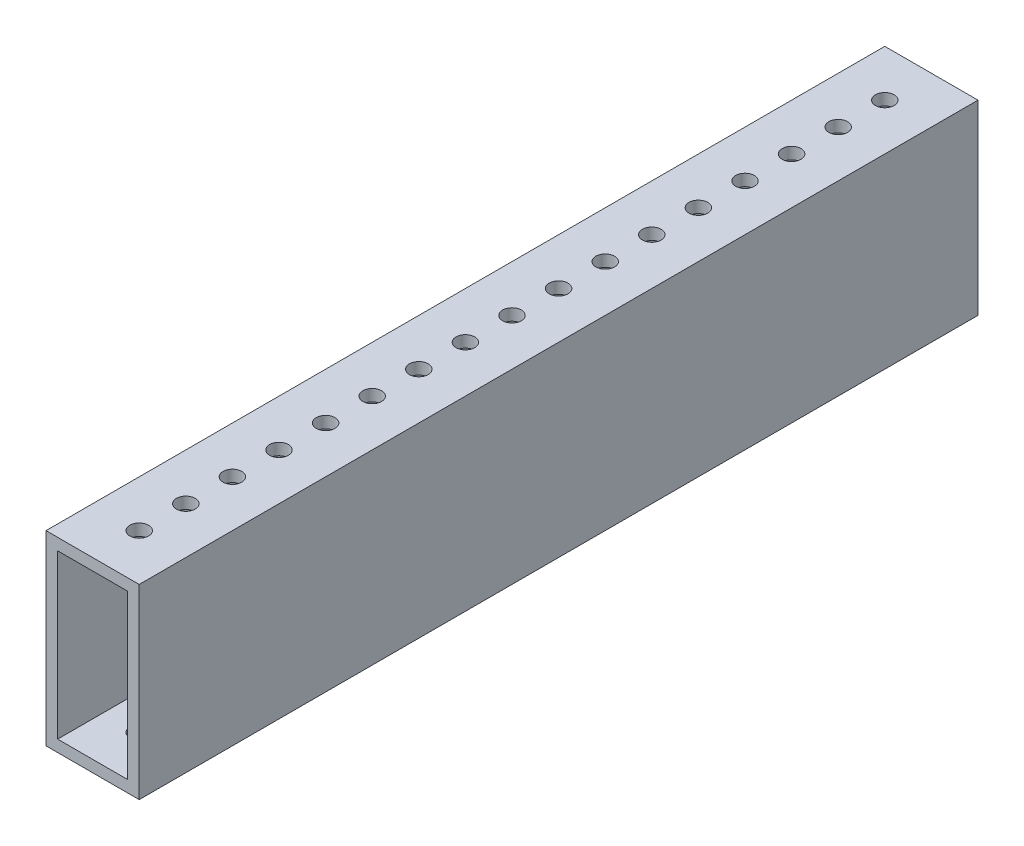
SolidWorks part; units mm, degrees
material "6061-T6 (SS)"
ref_plane "Front Plane" through (0, 0, 0) normal (0, 0, 1) x (1, 0, 0)
ref_plane "Top Plane" through (0, 0, 0) normal (0, 1, 0) x (1, 0, 0)
ref_plane "Right Plane" through (0, 0, 0) normal (1, 0, 0) x (0, 0, -1)
sketch "Sketch1" plane through (0, 0, 0) normal (0, 0, 1) x (1, 0, 0)
  line L0 (-9.525, 22.225) -> (9.525, 22.225)
  line L1 (-12.7, 25.4) -> (12.7, 25.4)
  line L2 (-12.7, 25.4) -> (-12.7, -25.4)
  line L3 (-12.7, -25.4) -> (12.7, -25.4)
  line L4 (12.7, 25.4) -> (12.7, -25.4)
  line L5 (9.525, 22.225) -> (9.525, -22.225)
  line L6 (-9.525, -22.225) -> (9.525, -22.225)
  line L7 (-9.525, 22.225) -> (-9.525, -22.225)
  line L8 (-12.7, 25.4) -> (12.7, -25.4) construction
  line L9 (12.7, 25.4) -> (-12.7, -25.4) construction
  point P5 (0, 0)
  dimension "D1" = 25.4
  dimension "D2" = 50.8
  dimension "D3" = 3.175
extrude "Boss-Extrude1" add sketch "Sketch1" along normal mid plane 228.6
sketch "Sketch2" plane through (0, 25.4, 0) normal (0, 1, 0) x (1, 0, 0)
  line L4 (12.7, -114.3) -> (-12.7, -114.3) construction
  circle A64 centre (0, -101.6) radius 2.5527
  circle A65 centre (0, -88.9) radius 2.5527
  circle A66 centre (0, -76.2) radius 2.5527
  circle A67 centre (0, -63.5) radius 2.5527
  circle A68 centre (0, -50.8) radius 2.5527
  circle A69 centre (0, -38.1) radius 2.5527
  circle A70 centre (0, -25.4) radius 2.5527
  circle A71 centre (0, -12.7) radius 2.5527
  circle A72 centre (0, 0) radius 2.5527
  circle A73 centre (0, 12.7) radius 2.5527
  circle A74 centre (0, 25.4) radius 2.5527
  circle A75 centre (0, 38.1) radius 2.5527
  circle A76 centre (0, 50.8) radius 2.5527
  circle A77 centre (0, 63.5) radius 2.5527
  circle A78 centre (0, 76.2) radius 2.5527
  circle A79 centre (0, 88.9) radius 2.5527
  circle A80 centre (0, 101.6) radius 2.5527
  circle A82 centre (0, 114.3) radius 2.5527 [skipped]
  dimension "D2" = 12.7
  dimension "D4" = 12.7
  dimension "D1" = 5.1054
  dimension "D3" = 18
extrude "Cut-Extrude1" cut sketch "Sketch2" against normal through all
